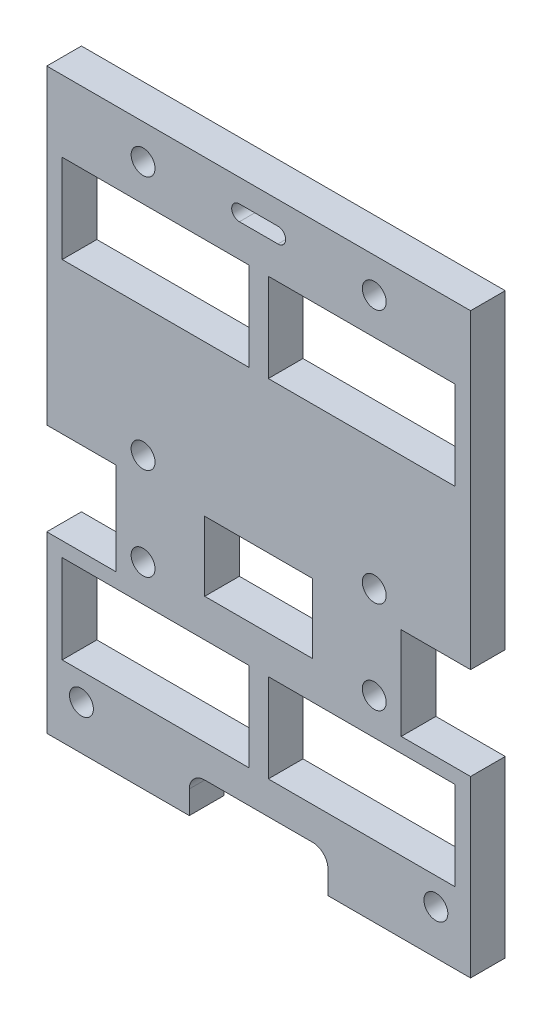
SolidWorks part; units mm, degrees
ref_plane "Front Plane" through (0, 0, 0) normal (0, 0, 1) x (1, 0, 0)
ref_plane "Top Plane" through (0, 0, 0) normal (0, 1, 0) x (1, 0, 0)
ref_plane "Right Plane" through (0, 0, 0) normal (1, 0, 0) x (0, 0, -1)
sketch "Sketch1" plane through (0, 0, 0) normal (0, 0, 1) x (1, 0, 0)
  line L0 (0, -37.5) -> (0, 37.5) construction
  line L1 (-27.5, -37.5) -> (27.5, -37.5)
  line L2 (-27.5, -37.5) -> (-27.5, 37.5)
  line L3 (-27.5, 37.5) -> (27.5, 37.5)
  line L4 (27.5, -37.5) -> (27.5, 37.5)
  line L5 (-27.5, -37.5) -> (27.5, 37.5) construction
  line L6 (-27.5, 37.5) -> (27.5, -37.5) construction
  line L7 (-27.5, 0) -> (27.5, 0) construction
  line L8 (-27.5, 22.5) -> (27.5, 22.5) construction
  line L9 (25.5, 16.75) -> (1.25, 28.25) construction
  line L10 (-25.5, 28.25) -> (-1.25, 28.25)
  line L11 (-25.5, 28.25) -> (-25.5, 16.75)
  line L12 (-25.5, 16.75) -> (-1.25, 16.75)
  line L13 (-1.25, 28.25) -> (-1.25, 16.75)
  line L14 (-25.5, 28.25) -> (-1.25, 16.75) construction
  line L15 (-25.5, 16.75) -> (-1.25, 28.25) construction
  line L16 (25.5, 28.25) -> (1.25, 16.75) construction
  line L17 (1.25, 28.25) -> (1.25, 16.75)
  line L18 (25.5, 16.75) -> (1.25, 16.75)
  line L19 (25.5, 28.25) -> (25.5, 16.75)
  line L20 (25.5, 28.25) -> (1.25, 28.25)
  line L21 (25.5, -28.25) -> (1.25, -16.75) construction
  line L22 (-25.5, -16.75) -> (-1.25, -28.25) construction
  line L23 (-25.5, -28.25) -> (-1.25, -16.75) construction
  line L24 (25.5, -16.75) -> (1.25, -28.25) construction
  line L25 (25.5, -28.25) -> (1.25, -28.25)
  line L26 (25.5, -28.25) -> (25.5, -16.75)
  line L27 (25.5, -16.75) -> (1.25, -16.75)
  line L28 (1.25, -28.25) -> (1.25, -16.75)
  line L29 (-1.25, -28.25) -> (-1.25, -16.75)
  line L30 (-25.5, -16.75) -> (-1.25, -16.75)
  line L31 (-25.5, -28.25) -> (-25.5, -16.75)
  line L32 (-25.5, -28.25) -> (-1.25, -28.25)
  point P0 (0, 0)
  point P12 (-13.375, 22.5)
  point P21 (13.375, 22.5)
  point P30 (13.375, -22.5)
  point P31 (-13.375, -22.5)
  dimension "D1" = 55
  dimension "D2" = 75
  dimension "D3" = 22.5
  dimension "D4" = 24.25
  dimension "D5" = 11.5
  dimension "D6" = 1.25
extrude "Boss-Extrude1" add sketch "Sketch1" along normal blind 4.5
sketch "Sketch2" plane through (0, 0, 4.5) normal (0, 0, 1) x (1, 0, 0)
  line L0 (0, -37.5) -> (0, 37.5) construction
  line L1 (-27.5, -37.5) -> (27.5, -37.5) construction
  line L2 (27.5, 37.5) -> (-27.5, 37.5) construction
  line L3 (-27.5, 0) -> (27.5, 0) construction
  line L4 (-27.5, 37.5) -> (-27.5, -37.5) construction
  line L5 (27.5, -37.5) -> (27.5, 37.5) construction
  line L6 (-15, 0) -> (15, 0) construction
  circle A0 centre (-15, 33) radius 1.55
  circle A1 centre (15, 33) radius 1.55
  circle A2 centre (15, 0) radius 1.55
  circle A3 centre (-15, 0) radius 1.55
  dimension "D1" = 3.1
  dimension "D7" = 3.1
  dimension "D8" = 3.1
  dimension "D2" = 15
  dimension "D3" = 33
  dimension "D4" = 30
  dimension "D5" = 15
  dimension "D6" = 0
extrude "screwHoles" cut sketch "Sketch2" against normal through all
sketch "Sketch3" plane through (0, 0, 4.5) normal (0, 0, 1) x (1, 0, 0)
  line L0 (-27.5, 9) -> (26.0486, 9) construction
  line L1 (-27.5, 37.5) -> (-27.5, -37.5) construction
  line L3 (0, 37.5) -> (0, -37.5) construction
  line L4 (27.5, 37.5) -> (-27.5, 37.5) construction
  line L5 (-27.5, -37.5) -> (27.5, -37.5) construction
  line L6 (19.1, 6.65) -> (8.9, 11.35) construction
  line L7 (-19.1, 11.35) -> (-8.9, 11.35)
  line L8 (-19.1, 11.35) -> (-19.1, 6.65)
  line L9 (-19.1, 6.65) -> (-8.9, 6.65)
  line L10 (-8.9, 11.35) -> (-8.9, 6.65)
  line L11 (-19.1, 11.35) -> (-8.9, 6.65) construction
  line L12 (-19.1, 6.65) -> (-8.9, 11.35) construction
  line L13 (19.1, 11.35) -> (8.9, 6.65) construction
  line L14 (8.9, 11.35) -> (8.9, 6.65)
  line L15 (19.1, 6.65) -> (8.9, 6.65)
  line L16 (19.1, 11.35) -> (19.1, 6.65)
  line L17 (19.1, 11.35) -> (8.9, 11.35)
  line L18 (-27.5, 37.5) -> (-27.5, -37.5) construction
  point P2 (-27.5, 0)
  point P12 (-14, 9)
  point P21 (14, 9)
  dimension "D1" = 10.2
  dimension "D2" = 4.7
  dimension "D3" = 14
  dimension "D4" = 9
extrude "BeltClamp" [suppressed] cut sketch "Sketch3" against normal through all
sketch "Sketch4" plane through (0, 0, 4.5) normal (0, 0, 1) x (1, 0, 0)
  line L0 (-27.5, 0) -> (27.5, 0) construction
  line L1 (-27.5, 37.5) -> (-27.5, -37.5) construction
  line L2 (27.5, -37.5) -> (27.5, 37.5) construction
  line L4 (-5.1, 2.35) -> (5.1, 2.35)
  line L5 (-5.1, 2.35) -> (-5.1, -2.35)
  line L6 (-5.1, -2.35) -> (5.1, -2.35)
  line L7 (5.1, 2.35) -> (5.1, -2.35)
  line L8 (-5.1, 2.35) -> (5.1, -2.35) construction
  line L9 (-5.1, -2.35) -> (5.1, 2.35) construction
  circle A0 centre (-15, 0) radius 1.55 construction
  point P6 (0, 0)
  dimension "D1" = 10.2
  dimension "D2" = 4.7
  dimension "D3" = 0
extrude "mountingPlateTab" [suppressed] cut sketch "Sketch4" against normal through all
sketch "Sketch5" plane through (0, 0, 4.5) normal (0, 0, 1) x (1, 0, 0)
  line L0 (-27.5, -9.75) -> (27.5, -9.75) construction
  line L1 (-27.5, 37.5) -> (-27.5, -37.5) construction
  line L2 (27.5, -37.5) -> (27.5, 37.5) construction
  line L4 (0, -37.5) -> (0, 37.5) construction
  line L5 (-27.5, -37.5) -> (27.5, -37.5) construction
  line L6 (27.5, 37.5) -> (-27.5, 37.5) construction
  line L7 (-20.65, -14.85) -> (-25.35, -4.65) construction
  line L8 (20.65, -4.65) -> (25.35, -4.65)
  line L9 (20.65, -4.65) -> (20.65, -14.85)
  line L10 (20.65, -14.85) -> (25.35, -14.85)
  line L11 (25.35, -4.65) -> (25.35, -14.85)
  line L12 (20.65, -4.65) -> (25.35, -14.85) construction
  line L13 (20.65, -14.85) -> (25.35, -4.65) construction
  line L14 (-20.65, -4.65) -> (-25.35, -14.85) construction
  line L15 (-25.35, -4.65) -> (-25.35, -14.85)
  line L16 (-20.65, -14.85) -> (-25.35, -14.85)
  line L17 (-20.65, -4.65) -> (-20.65, -14.85)
  line L18 (-20.65, -4.65) -> (-25.35, -4.65)
  line L19 (23, -9.75) -> (23, -37.5) construction
  line L20 (-23, -9.75) -> (-23, -37.5) construction
  circle A0 centre (23, -31.75) radius 1.55
  circle A1 centre (-23, -31.75) radius 1.55
  point P15 (23, -9.75)
  point P24 (-23, -9.75)
  dimension "D5" = 3.1
  dimension "D2" = 10.2
  dimension "D3" = 4.7
  dimension "D4" = 23
  dimension "D6" = 22
  dimension "D1" = 9.75
extrude "BraceTabs" cut sketch "Sketch5" against normal through all
sketch "Sketch6" [suppressed] plane through (0, 0, 4.5) normal (0, 0, 1) x (1, 0, 0)
  line L0 (-25.35, -9.75) -> (25.35, -9.75) construction
  line L1 (-25.35, -4.65) -> (-25.35, -14.85) construction
  line L2 (25.35, -14.85) -> (25.35, -4.65) construction
  line L3 (0, -2.35) -> (0, -37.5) construction
  line L4 (-5.1, -2.35) -> (5.1, -2.35) construction
  line L5 (-27.5, -37.5) -> (27.5, -37.5) construction
  line L6 (23, -14.85) -> (23, -4.65) construction
  line L7 (20.65, -14.85) -> (25.35, -14.85) construction
  line L8 (25.35, -4.65) -> (20.65, -4.65) construction
  line L9 (20.65, -4.65) -> (20.65, -14.85) construction
  line L10 (19.65, -15.85) -> (26.35, -15.85)
  line L11 (19.65, -15.85) -> (19.65, -3.65)
  line L12 (19.65, -3.65) -> (26.35, -3.65)
  line L13 (26.35, -15.85) -> (26.35, -3.65)
  line L14 (19.65, -15.85) -> (26.35, -3.65) construction
  line L15 (19.65, -3.65) -> (26.35, -15.85) construction
  line L16 (-19.65, -3.65) -> (-26.35, -15.85) construction
  line L17 (-19.65, -15.85) -> (-26.35, -3.65) construction
  line L18 (-23, -14.85) -> (-23, -4.65) construction
  line L19 (-26.35, -15.85) -> (-26.35, -3.65)
  line L20 (-19.65, -3.65) -> (-26.35, -3.65)
  line L21 (-19.65, -15.85) -> (-19.65, -3.65)
  line L22 (-19.65, -15.85) -> (-26.35, -15.85)
  circle A0 centre (23, -9.75) radius 1.55
  circle A1 centre (-23, -9.75) radius 1.55
  point P18 (23, -9.75)
  dimension "D3" = 3.1
  dimension "D1" = 1
  dimension "D2" = 1
extrude "FrontToRear1" [suppressed] add sketch "Sketch6" against normal up to surface (4.5 mm away) up to face at (-24.55, -31.75, 0)
sketch "Sketch7" [suppressed] plane through (0, 0, 4.5) normal (0, 0, 1) x (1, 0, 0)
  line L0 (5.1, 2.35) -> (-5.1, 2.35) construction
  line L1 (-20, -3.35) -> (20, -3.35)
  line L2 (-20, -3.35) -> (-20, 3.35)
  line L3 (-20, 3.35) -> (20, 3.35)
  line L4 (20, -3.35) -> (20, 3.35)
  line L5 (-20, -3.35) -> (20, 3.35) construction
  line L6 (-20, 3.35) -> (20, -3.35) construction
  circle A0 centre (15, 0) radius 1.55 construction
  point P0 (0, 0)
  dimension "D1" = 1
  dimension "D2" = 5
extrude "FrontToRear2" [suppressed] add sketch "Sketch7" against normal through all
sketch "Sketch8" plane through (0, 0, 4.5) normal (0, 0, 1) x (1, 0, 0)
  line L0 (-27.5, -12) -> (27.5, -12) construction
  line L1 (-27.5, 37.5) -> (-27.5, -37.5) construction
  line L2 (27.5, -37.5) -> (27.5, 37.5) construction
  line L3 (0, -37.5) -> (0, 0) construction
  line L4 (-27.5, -37.5) -> (27.5, -37.5) construction
  circle A0 centre (-15, -12) radius 1.55
  circle A1 centre (15, -12) radius 1.55
  dimension "D2" = 3.1
  dimension "D1" = 12
  dimension "D3" = 15
extrude "ExpansionScrewholes" cut sketch "Sketch8" against normal through all
sketch "Sketch12" plane through (0, 0, 4.5) normal (0, 0, 1) x (1, 0, 0)
  line L0 (0, 37.5) -> (0, 0) construction
  line L1 (27.5, 37.5) -> (-27.5, 37.5) construction
  line L2 (-2.5, 33.5) -> (2.5, 33.5) construction
  line L3 (-2.5, 34.5) -> (2.5, 34.5)
  line L4 (-2.5, 32.5) -> (2.5, 32.5)
  arc A0 (-2.5, 34.5) -> (-2.5, 32.5) centre (-2.5, 33.5) ccw
  arc A1 (2.5, 32.5) -> (2.5, 34.5) centre (2.5, 33.5) ccw
  point P7 (0, 33.5)
  dimension "D1" = 3
  dimension "D2" = 2
  dimension "D3" = 5
extrude "CableTieSlot" cut sketch "Sketch12" against normal through all
sketch "Sketch11" plane through (0, 0, 4.5) normal (0, 0, 1) x (1, 0, 0)
  line L0 (13.5615, -8.85) -> (27.5, -8.85) construction
  line L1 (27.5, -37.5) -> (27.5, 37.5) construction
  line L2 (0, 37.5) -> (0, -37.5) construction
  line L3 (36.5, -14.85) -> (18.5, -14.85)
  line L4 (36.5, -14.85) -> (36.5, -2.85)
  line L5 (36.5, -2.85) -> (18.5, -2.85)
  line L6 (18.5, -14.85) -> (18.5, -2.85)
  line L7 (36.5, -14.85) -> (18.5, -2.85) construction
  line L8 (36.5, -2.85) -> (18.5, -14.85) construction
  line L11 (-36.5, -2.85) -> (-18.5, -14.85) construction
  line L12 (-36.5, -14.85) -> (-18.5, -2.85) construction
  line L13 (-18.5, -14.85) -> (-18.5, -2.85)
  line L14 (-36.5, -2.85) -> (-18.5, -2.85)
  line L15 (-36.5, -14.85) -> (-36.5, -2.85)
  line L16 (-36.5, -14.85) -> (-18.5, -14.85)
  line L17 (36.5, -2.85) -> (18.5, -14.85) construction
  line L18 (20.65, -14.85) -> (25.35, -14.85) construction
  line L19 (27.5, 37.5) -> (-27.5, 37.5) construction
  line L20 (-27.5, -37.5) -> (27.5, -37.5) construction
  dimension "D1" = 9
  dimension "D2" = 12
  dimension "D3" = 0
extrude "Cut-Extrude2" cut sketch "Sketch11" against normal through all
sketch "Sketch10" [suppressed] plane through (0, 0, 4.5) normal (0, 0, 1) x (1, 0, 0)
  line L0 (4.7446, 1) -> (27.5, 1) construction
  line L1 (-5.1, 0) -> (5.1, 0) construction
  line L2 (27.5, -37.5) -> (27.5, -14.85) construction
  line L3 (0, 2.35) -> (0, -2.35) construction
  line L4 (36.5, 4) -> (18.5, 4)
  line L5 (36.5, 4) -> (36.5, -2)
  line L6 (36.5, -2) -> (18.5, -2)
  line L7 (18.5, 4) -> (18.5, -2)
  line L8 (36.5, 4) -> (18.5, -2) construction
  line L9 (36.5, -2) -> (18.5, 4) construction
  line L10 (5.1, 2.35) -> (-5.1, 2.35) construction
  line L11 (-5.1, -2.35) -> (5.1, -2.35) construction
  line L12 (-36.5, -2) -> (-18.5, 4) construction
  line L13 (-36.5, 4) -> (-18.5, -2) construction
  line L14 (-4.7446, 1) -> (-27.5, 1) construction
  line L15 (-18.5, 4) -> (-18.5, -2)
  line L16 (-36.5, -2) -> (-18.5, -2)
  line L17 (-36.5, 4) -> (-36.5, -2)
  line L18 (-36.5, 4) -> (-18.5, 4)
  line L19 (36.5, -2) -> (18.5, 4) construction
  line L20 (-5.1, 2.35) -> (-5.1, -2.35) construction
  line L21 (5.1, -2.35) -> (5.1, 2.35) construction
  dimension "D1" = 6
  dimension "D2" = 9
  dimension "D3" = 1
extrude "CableTieSlots" [suppressed] cut sketch "Sketch10" against normal through all
sketch "Sketch9" plane through (0, 0, 4.5) normal (0, 0, 1) x (1, 0, 0)
  line L0 (-27.5, -37.5) -> (27.5, -37.5) construction
  line L5 (-9, -42.5) -> (9, -42.5)
  line L6 (-9, -42.5) -> (-9, -34.5)
  line L7 (-7, -32.5) -> (7, -32.5)
  line L8 (9, -42.5) -> (9, -34.5)
  line L9 (-9, -42.5) -> (9, -32.5) construction
  line L10 (-9, -32.5) -> (9, -42.5) construction
  arc A0 (7, -32.5) -> (9, -34.5) centre (7, -34.5) cw
  arc A1 (-9, -34.5) -> (-7, -32.5) centre (-7, -34.5) cw
  point P9 (0, -37.5)
  line M42 (-27.5, -37.5) -> (27.5, -37.5)
  dimension "D3" = 2
  dimension "D1" = 18
  dimension "D2" = 5
extrude "RearFanSlot" cut sketch "Sketch9" against normal through all contours A1 L6 L8 A0 L7 M42 | L5 L8 L6 M42
sketch "Sketch13" plane through (0, 0, 4.5) normal (0, 0, 1) x (1, 0, 0)
  line L1 (-7, -2.85) -> (7, -2.85)
  line L2 (-7, -2.85) -> (-7, -11.85)
  line L3 (-7, -11.85) -> (7, -11.85)
  line L4 (7, -2.85) -> (7, -11.85)
  line L5 (-7, -2.85) -> (7, -11.85) construction
  line L6 (-7, -11.85) -> (7, -2.85) construction
  line L9 (0, 37.5) -> (0, -7.35) construction
  line L10 (-18.5, -2.85) -> (-27.5, -2.85) construction
  line L11 (27.5, 37.5) -> (-27.5, 37.5) construction
  line L13 (-27.5, -14.85) -> (-18.5, -14.85) construction
  point P0 (0, -7.35)
  dimension "D1" = 3
  dimension "D2" = 0
  dimension "D3" = 7
extrude "Cut-Extrude3" cut sketch "Sketch13" against normal through all
equation "\"X-ROD-SPACING\"=45"
equation "\"Y-ROD-SPACING\"=75"
equation "\"Z-ROD-SPACING\"=17.5"
equation "\"Y-BED-OFFSET\"=2"
equation "\"Y-BED-ROD-INSET\"=3.5"
equation "\"Y-BED-SCREW-SPACING\"=209"
equation "\"Y-BED-SCREW-CUTOUT-SLOT-HEIGHT\"=2"
equation "\"T-SLOT-NUT-FILLET-RADIUS\"=0.25"
equation "\"T-SLOT-SCREW-SHAFT-RADIUS\"=1.75"
equation "\"T-SLOT-SCREW-SHAFT-CUTOUT-LENGTH\"=10.5"
equation "\"T-SLOT-NUT-DEPTH\"=4.2"
equation "\"T-SLOT-NUT-WIDTH\"=3"
equation "\"T-SLOT-NUT-END-DISTANCE\"=8"
equation "\"ACRYLIC-THICKNESS\"=10"
equation "\"ACRYLIC-THICKNESS2\"=4.5"
equation "\"ACRYLIC-TAB-CUTOUT-SIZE\"=\"ACRYLIC-THICKNESS\"+\"ACRYLIC-TAB-TOLERANCE\"*2"
equation "\"ACRYLIC-TAB-WIDTH\"=\"ACRYLIC-THICKNESS\""
equation "\"ACRYLIC-M3-HOLE\"=3.1"
equation "\"SMOOTHROD-CAP-SCREW-DISTANCE\"=20"
equation "\"FRAME-WIDTH-INNER\"=370"
equation "\"NEMA17-HOLE-SPACING\"=31"
equation "\"NEMA17-CENTRAL-CUTOUT\"=22.5"
equation "\"Z-BRACKET-REACH\"=55"
equation "\"Z-ROD-INSET\"=16"
equation "\"TOP-BRACKET-SPACING\"=40"
equation "\"SMOOTHROD-X-LENGTH\"=350"
equation "\"SMOOTHROD-Y-LENGTH\"=350"
equation "\"SMOOTHROD-Z-LENGTH\"=350"
equation "\"SMOOTHROD-TIGHTENING-HEADROOM\"=.25"
equation "\"LEADSCREW-Z-LENGTH\"=300"
equation "\"SCREW-LENGTH-FRAME\"=\"ACRYLIC-THICKNESS\" + 10"
equation "\"SCREW-LENGTH-MOTOR\"=\"ACRYLIC-THICKNESS\" + 5"
equation "\"SCREW-HEAD-RADIUS\"=6"
equation "\"PRINTED-X-SMOOTHROD-DIAMETER\"=8.2"
equation "\"PRINTED-X-SMOOTHROD-CUTOUT\"=10"
equation "\"PRINTED-X-BASE-HEIGHT\"=10"
equation "\"PRINTED-LM8UU-CUTOUT-SIZE\"=15.25"
equation "\"PRINTED-LM8UU-CUTOUT-LENGTH\"=24.5"
equation "\"PRINTED-X-IDLER-HEIGHT\"=16"
equation "\"PSU-MOUNTING-WIDTH\"=95"
equation "\"PSU-MOUNTING-HEIGHT\"=177"
equation "\"Y-BELT-TO-ROD-DISTANCE\"=20"
equation "\"SPOOL-HOLDER-ROD-SPACING\"=150"
equation "\"D3@Sketch1\"=\"X-ROD-SPACING\"/2"
equation "\"D4@Sketch1\"=\"ACRYLIC-X-CARRIAGE-LM8UU-CUTOUT-WIDTH\""
equation "\"D1@Boss-Extrude1\"=\"ACRYLIC-THICKNESS2\""
equation "\"D1@Sketch2\"=\"ACRYLIC-M3-HOLE\""
equation "\"D1@Sketch3\"=\"ACRYLIC-TAB-CUTOUT-SIZE\""
equation "\"D2@Sketch3\"=\"ACRYLIC-THICKNESS2\"+\"ACRYLIC-TAB-TOLERANCE\"*2"
equation "\"ACRYLIC-X-CARRIAGE-WIDTH\"=55"
equation "\"ACRYLIC-X-CARRIAGE-HEIGHT\"=75"
equation "\"D1@Sketch1\"=\"ACRYLIC-X-CARRIAGE-WIDTH\""
equation "\"D2@Sketch1\"=\"ACRYLIC-X-CARRIAGE-HEIGHT\""
equation "\"ACRYLIC-X-CARRIAGE-CENTER-TAB-SPACING\"=14"
equation "\"D3@Sketch3\"=\"ACRYLIC-X-CARRIAGE-CENTER-TAB-SPACING\""
equation "\"SCREW-LENGTH-EXTRUDER\"=28"
equation "\"ACRYLIC-X-CARRIAGE-SCREW-SPACING-X\"=15"
equation "\"ACRYLIC-X-CARRIAGE-SCREW-SPACING-Y\"=33"
equation "\"D2@Sketch2\"=\"ACRYLIC-X-CARRIAGE-SCREW-SPACING-X\""
equation "\"D3@Sketch2\"=\"ACRYLIC-X-CARRIAGE-SCREW-SPACING-Y\""
equation "\"D1@Sketch4\"=\"ACRYLIC-TAB-CUTOUT-SIZE\""
equation "\"D2@Sketch4\"=\"ACRYLIC-THICKNESS2\"+\"ACRYLIC-TAB-TOLERANCE\"*2"
equation "\"D2@Sketch5\"=\"ACRYLIC-TAB-CUTOUT-SIZE\""
equation "\"D3@Sketch5\"=\"ACRYLIC-THICKNESS2\"+\"ACRYLIC-TAB-TOLERANCE\"*2"
equation "\"ACRYLIC-X-CARRIAGE-EXTRUDER-SHELF-DEPTH\"=\"ACRYLIC-X-CARRIAGE-EXTRUDER-OFFSET\" + 28"
equation "\"ACRYLIC-X-CARRIAGE-EXTRUDER-BRACE-SPACING\"=23"
equation "\"D4@Sketch5\"=\"ACRYLIC-X-CARRIAGE-EXTRUDER-BRACE-SPACING\""
equation "\"D4@Sketch2\"=\"ACRYLIC-X-CARRIAGE-SCREW-SPACING-X\"*2"
equation "\"D5@Sketch2\"=\"ACRYLIC-X-CARRIAGE-SCREW-SPACING-X\""
equation "\"D7@Sketch2\"=\"ACRYLIC-M3-HOLE\""
equation "\"D8@Sketch2\"=\"ACRYLIC-M3-HOLE\""
equation "\"ACRYLIC-X-CARRIAGE-LM8UU-CUTOUT-WIDTH\"=24.25"
equation "\"ACRYLIC-TAB-TOLERANCE\"=.1"
equation "\"ACRYLIC-X-CARRIAGE-EXTRUDER-OFFSET\"=26"
equation "\"ACRYLIC-X-CARRIAGE-EXTRUDER-ANGLE\"=90"
equation "\"ACRYLIC-X-CARRIAGE-EXTRUDER-BRACE-TAB-OFFSET\"=20"
equation "\"ACRYLIC-X-CARRIAGE-EXTRUDER-BRACE-HEIGHT\"=35"
equation "\"ACRYLIC-X-CARRIAGE-EXTRUDER-BRACE-SCREW-SPACING\"=22"
equation "\"D5@Sketch5\"=\"ACRYLIC-M3-HOLE\""
equation "\"D3@Sketch6\"=\"ACRYLIC-M3-HOLE\""
equation "\"ACRYLIC-X-CARRIAGE-LM8UU-CUTOUT-HEIGHT\"=11.5"
equation "\"ACRYLIC-X-CARRIAGE-DUAL-WIDTH-MULTIPLIER\"=1.65"
equation "\"ACRYLIC-X-CARRIAGE-DUAL-HOTEND-SPACING\"=42"
equation "\"ACRYLIC-X-CARRIAGE-DUAL-WIDTH\"=103"
equation "\"ACRYLIC-X-CARRIAGE-DUAL-HOTEND-SEPARATION\"=35"
equation "\"ACRYLIC-X-CARRIAGE-DUAL-MOUNT-PLATE-DEPTH\"=76"
equation "\"ACRYLIC-X-CARRIAGE-DUAL-MOUNT-BRACE-WIDTH\"=45"
equation "\"ACRYLIC-X-CARRIAGE-DUAL-MOUNT-SCREW-WIDTH\"=40"
equation "\"D5@Sketch1\"=\"ACRYLIC-X-CARRIAGE-LM8UU-CUTOUT-HEIGHT\""
equation "\"D2@Sketch8\"=\"ACRYLIC-M3-HOLE\""
equation "\"D1@Sketch5\"=\"ACRYLIC-THICKNESS2\"/2 + 7.5"
